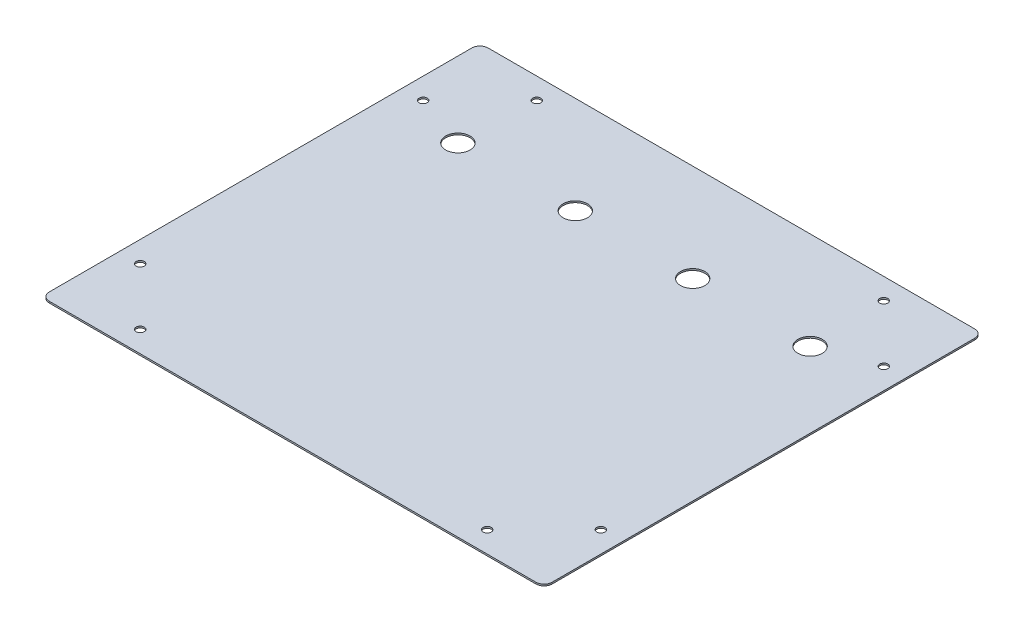
SolidWorks part; units mm, degrees
ref_plane "Front Plane" through (0, 0, 0) normal (0, 0, 1) x (1, 0, 0)
ref_plane "Top Plane" through (0, 0, 0) normal (0, 1, 0) x (1, 0, 0)
ref_plane "Right Plane" through (0, 0, 0) normal (1, 0, 0) x (0, 0, -1)
sketch "Sketch1" plane through (0, 0, 0) normal (0, 1, 0) x (1, 0, 0)
  line L1 (154.9, -135.17) -> (-154.9, -135.17)
  line L2 (154.9, -135.17) -> (154.9, 135.17)
  line L3 (154.9, 135.17) -> (-154.9, 135.17)
  line L4 (-154.9, -135.17) -> (-154.9, 135.17)
  line L5 (154.9, -135.17) -> (-154.9, 135.17) construction
  line L6 (154.9, 135.17) -> (-154.9, -135.17) construction
  point P0 (0, 0)
  dimension "D1" = 270.34
  dimension "D2" = 309.8
base flange "Base-Flange1" sketch "Sketch1" thickness 1 reverse thickness direction no parameters "D1"=0.7366
fillet "Fillet1" radius 5 4 edges at (-154.9, -0.5, 135.17) (-154.9, -0.5, -135.17) (154.9, -0.5, -135.17) (154.9, -0.5, 135.17)
sketch "Sketch2" plane through (0, -1, 0) normal (0, -1, 0) x (1, 0, 0)
  line L0 (0, 195.235) -> (0, 0) construction
  line L1 (-149.9, 135.17) -> (149.9, 135.17) construction
  line L2 (-154.9, -130.17) -> (-154.9, 130.17) construction
  line L3 (0, 0) -> (-223.8435, 0) construction
  line L4 (154.9, 130.17) -> (154.9, -130.17) construction
  line L5 (149.9, -135.17) -> (-149.9, -135.17) construction
  line L12 (-141.9, 122.1695) -> (-141.9, -122.17) construction
  line L13 (-141.9, -122.17) -> (141.9, -122.17) construction
  line L14 (141.9, -122.17) -> (141.9, 122.1695) construction
  line L16 (141.9, 122.1695) -> (-141.9, 122.1695) construction
  circle A0 centre (-141.9, 87.1695) radius 2.5
  circle A1 centre (-106.9, 122.1695) radius 2.5
  circle A2 centre (141.9, 87.1695) radius 2.5
  circle A3 centre (106.9, 122.1695) radius 2.5
  circle A4 centre (141.9, -87.1695) radius 2.5
  circle A5 centre (106.9, -122.1695) radius 2.5
  circle A6 centre (-141.9, -87.1695) radius 2.5
  circle A7 centre (-106.9, -122.1695) radius 2.5
  dimension "D1" = 5
  dimension "D2" = 5
  dimension "D3" = 35
  dimension "D4" = 35
  dimension "D5" = 13.0005
  dimension "D6" = 13
  dimension "D7" = 13
  dimension "D8" = 13
extrude "Cut-Extrude1" cut sketch "Sketch2" against normal blind 10 normal cut yes
sketch "Sketch4" plane through (0, -1, 0) normal (0, -1, 0) x (-1, 0, 0)
  line L0 (108.5, 75.17) -> (-108.5, 75.17) construction
  line L1 (-154.9, 135.17) -> (154.9, 135.17) construction
  circle A0 centre (108.5, 75.17) radius 7.5
  circle A1 centre (36.1667, 75.17) radius 7.5
  circle A2 centre (-36.1667, 75.17) radius 7.5
  circle A3 centre (-108.5, 75.17) radius 7.5
  dimension "D1" = 15
  dimension "D3" = 72.3333
  dimension "D4" = 72.3333
  dimension "D2" = 60
extrude "Cut-Extrude2" cut sketch "Sketch4" against normal blind 10 normal cut yes
sketch "Bend-Lines1" [suppressed] plane through (0, 0, 0) normal (0, 1, 0) x (1, 0, 0)
sketch "Bounding-Box1" [suppressed] plane through (0, 0, 0) normal (0, 1, 0) x (1, 0, 0)
sheet metal parameters "Sheet-Metal1" thickness 1 parameters "D1"=0.7366
flat pattern "Flat-Pattern1" [suppressed]
sketch "Bend-Lines2" plane through (0, 0, 0) normal (0, 1, 0) x (1, 0, 0)
sketch3d "Bounding-Box2" [suppressed]
  line L0 (-154.9, -135.17, 0) -> (154.9, -135.17, 0) construction
  line L1 (-154.9, 135.17, 0) -> (154.9, 135.17, 0) construction
  line L2 (-154.9, -135.17, 0) -> (-154.9, 135.17, 0) construction
  line L3 (154.9, -135.17, 0) -> (154.9, 135.17, 0) construction
sheet metal parameters "Sheet-Metal2" thickness 1 parameters "D1"=0.7366
flat pattern "Flat-Pattern1"
sketch "Bend-Lines2" plane through (0, 0, 0) normal (0, 1, 0) x (1, 0, 0)
sketch3d "Bounding-Box2" [suppressed]
  line L0 (-154.9, -135.17, 0) -> (154.9, -135.17, 0) construction
  line L1 (-154.9, 135.17, 0) -> (154.9, 135.17, 0) construction
  line L2 (-154.9, -135.17, 0) -> (-154.9, 135.17, 0) construction
  line L3 (154.9, -135.17, 0) -> (154.9, 135.17, 0) construction
sheet metal parameters "Sheet-Metal3" thickness 1 parameters "D1"=0.7366
flat pattern "Flat-Pattern1"
sketch "Bend-Lines2" plane through (0, 0, 0) normal (0, 1, 0) x (1, 0, 0)
sketch3d "Bounding-Box2" [suppressed]
  line L0 (-154.9, -135.17, 0) -> (154.9, -135.17, 0) construction
  line L1 (-154.9, 135.17, 0) -> (154.9, 135.17, 0) construction
  line L2 (-154.9, -135.17, 0) -> (-154.9, 135.17, 0) construction
  line L3 (154.9, -135.17, 0) -> (154.9, 135.17, 0) construction
